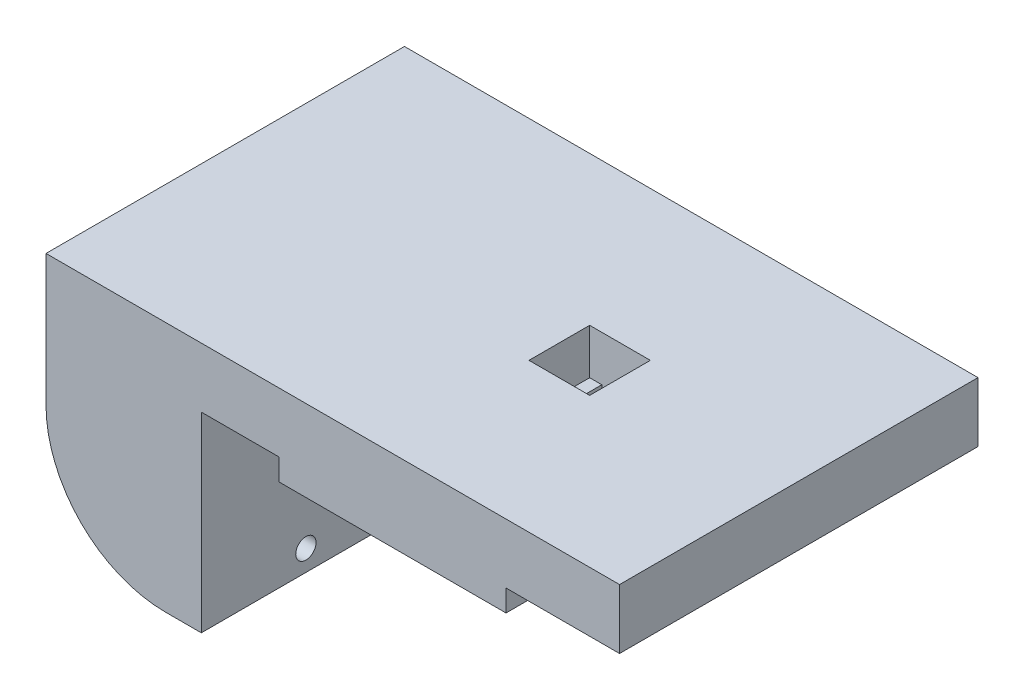
SolidWorks part; units mm, degrees
ref_plane "Front Plane" through (0, 0, 0) normal (0, 0, 1) x (1, 0, 0)
ref_plane "Top Plane" through (0, 0, 0) normal (0, 1, 0) x (1, 0, 0)
ref_plane "Right Plane" through (0, 0, 0) normal (1, 0, 0) x (0, 0, -1)
sketch "Sketch1" plane through (0, 0, 0) normal (0, 1, 0) x (1, 0, 0)
  line L1 (0, 0) -> (76, 0)
  line L2 (0, 0) -> (0, 60)
  line L3 (0, 60) -> (76, 60)
  line L4 (76, 0) -> (76, 60)
  dimension "D1" = 76
  dimension "D2" = 60
extrude "Boss-Extrude1" add sketch "Sketch1" along normal blind 10
sketch "Sketch2" plane through (0, 0, 0) normal (0, -1, 0) x (1, 0, 0)
  line L0 (0, 0) -> (76, 0) construction
  line L1 (0, -60) -> (6, -60)
  line L2 (0, -60) -> (0, 0)
  line L3 (0, 0) -> (6, 0)
  line L4 (6, -60) -> (6, 0)
  dimension "D1" = 6
extrude "Boss-Extrude2" add sketch "Sketch2" along normal blind 32
sketch "Sketch3" plane through (0, 0, 0) normal (-1, 0, 0) x (0, 0, 1)
  line L0 (0, -16) -> (-60, -16) construction
  line L1 (0, 10) -> (0, -32) construction
  line L2 (-60, 10) -> (-60, -32) construction
  line L5 (-60, -32) -> (-60, 0) construction
  line L6 (-17.5, -3.5) -> (-42.5, -3.5)
  line L7 (-17.5, -3.5) -> (-17.5, -28.5)
  line L8 (-17.5, -28.5) -> (-42.5, -28.5)
  line L9 (-42.5, -3.5) -> (-42.5, -28.5)
  line L10 (-17.5, -3.5) -> (-42.5, -28.5) construction
  line L11 (-17.5, -28.5) -> (-42.5, -3.5) construction
  point P7 (-30, -16)
  point P10 (0, 0)
  dimension "D1" = 25
hole_wizard "M3 Clearance Hole1" positions "Sketch4" profile "Sketch5" hole size "M3" standard "ANSI Metric" end condition through all
sketch "Sketch4" plane through (0, 0, 0) normal (-1, 0, 0) x (0, 0, 1)
  point P0 (-42.5, -28.5)
  point P3 (-42.5, -3.5)
  point P6 (-17.5, -3.5)
  point P9 (-17.5, -28.5)
sketch "Sketch5" plane through (0, -28.5, -42.5) normal (0, 1, 0) x (0, 0, 1)
  line L0 (0, 0) -> (0, 76)
  line L1 (0, 76) -> (1.7, 76)
  line L2 (1.7, 76) -> (1.7, 0)
  line L5 (1.7, 0) -> (0, 0)
  line L11 (0, -6.35) -> (0, 107.95) construction
  dimension "Thru Hole Dia." = 3.4
  dimension "Thru Hole Depth" = 76
ref_plane "Plane1" through (0, -16, 0) normal (0, -1, 0) x (-1, 0, 0)
ref_plane "Plane2" through (0, -4, 0) normal (0, -1, 0) x (-1, 0, 0)
ref_plane "Belt Plane" through (0, -3.624, 0) normal (0, -1, 0) x (-1, 0, 0)
sketch "Sketch7" plane through (0, 0, 0) normal (0, -1, 0) x (1, 0, 0)
  line L0 (76, -60) -> (6, -60) construction
  line L1 (19, -60) -> (57, -60)
  line L2 (19, -60) -> (19, 0)
  line L3 (19, 0) -> (57, 0)
  line L4 (57, -60) -> (57, 0)
  line L5 (6, 0) -> (76, 0) construction
  line L6 (6, -60) -> (6, 0) construction
  line L8 (76, 0) -> (76, -60) construction
  dimension "D1" = 13
  dimension "D2" = 19
extrude "Boss-Extrude3" add sketch "Sketch7" along normal up to surface (3.624 mm away) up to plane "Belt Plane"
sketch "Sketch8" plane through (0, -3.624, 0) normal (0, -1, 0) x (1, 0, 0)
  line L0 (41, -60) -> (41, 0) construction
  line L1 (19, -60) -> (57, -60) construction
  line L2 (57, 0) -> (19, 0) construction
  line L4 (6, -60) -> (6, 0) construction
  point P4 (0, 0)
  dimension "D1" = 35
hole_wizard "M4 Clearance Hole1" positions "Sketch9" profile "Sketch10" hole size "M4" standard "ANSI Metric" end condition through all
sketch "Sketch9" plane through (0, -3.624, 0) normal (0, -1, 0) x (-1, 0, 0)
  line L0 (-41, 60) -> (-41, 0) construction
  point P0 (-41, 30)
  point P5 (0, 0)
sketch "Sketch10" plane through (41, -3.624, -30) normal (1, 0, 0) x (0, 0, -1)
  line L0 (0, 0) -> (0, 13.624)
  line L1 (0, 13.624) -> (2.25, 13.624)
  line L2 (2.25, 13.624) -> (2.25, 0)
  line L5 (2.25, 0) -> (0, 0)
  line L11 (0, -6.35) -> (0, 107.95) construction
  dimension "Thru Hole Dia." = 4.5
  dimension "Thru Hole Depth" = 13.624
sketch "Sketch11" plane through (0, 10, 0) normal (0, 1, 0) x (1, 0, 0)
  line L1 (35.92, 24.92) -> (46.08, 24.92)
  line L2 (35.92, 24.92) -> (35.92, 35.08)
  line L3 (35.92, 35.08) -> (46.08, 35.08)
  line L4 (46.08, 24.92) -> (46.08, 35.08)
  line L5 (35.92, 24.92) -> (46.08, 35.08) construction
  line L6 (35.92, 35.08) -> (46.08, 24.92) construction
  point P0 (41, 30)
  dimension "D1" = 10.16
extrude "Cut-Extrude1" cut sketch "Sketch11" against normal offset from surface (9.124 mm away) 4.5 up to face at (41, -3.624, -32.25)
sketch "Sketch12" plane through (0, 0.876, 0) normal (0, 1, 0) x (1, 0, 0)
  line L0 (46.08, 35.08) -> (35.92, 35.08) construction
  line L1 (35.92, 24.92) -> (37.952, 24.92)
  line L2 (35.92, 24.92) -> (35.92, 35.08)
  line L3 (35.92, 35.08) -> (37.952, 35.08)
  line L4 (37.952, 24.92) -> (37.952, 35.08)
  line L6 (46.08, 24.92) -> (44.048, 24.92)
  line L7 (46.08, 24.92) -> (46.08, 35.08)
  line L8 (46.08, 35.08) -> (44.048, 35.08)
  line L9 (44.048, 24.92) -> (44.048, 35.08)
  dimension "D1" = 6.096
extrude "Boss-Extrude4" add sketch "Sketch12" along normal blind 1.524
ref_plane "Plane4" through (38, 0, 0) normal (-1, 0, 0) x (0, 0, 1)
sketch "Sketch13" plane through (0, 0, 0) normal (-1, 0, 0) x (0, 0, 1)
  line L0 (-60, 10) -> (-60, -32) construction
  line L1 (0, 10) -> (-60, 10)
  line L2 (0, 10) -> (0, 5)
  line L3 (0, 5) -> (-60, 5)
  line L4 (-60, 10) -> (-60, 5)
  dimension "D1" = 5
extrude "Boss-Extrude5" add sketch "Sketch13" along normal blind 20
sketch "Sketch14" plane through (0, -32, 0) normal (0, -1, 0) x (1, 0, 0)
  line L1 (0, -60) -> (-20, -60)
  line L2 (0, -60) -> (0, -55)
  line L3 (0, -55) -> (-20, -55)
  line L4 (-20, -60) -> (-20, -55)
  line L5 (0, 0) -> (-20, 0)
  line L6 (0, 0) -> (0, -5)
  line L7 (0, -5) -> (-20, -5)
  line L8 (-20, 0) -> (-20, -5)
  line L9 (-20, -60) -> (-20, 0) construction
  dimension "D1" = 5
extrude "Boss-Extrude6" add sketch "Sketch14" against normal up to next
fillet "Fillet1" radius 20 2 edges at (-20, -32, -2.5) (-20, -32, -57.5)
